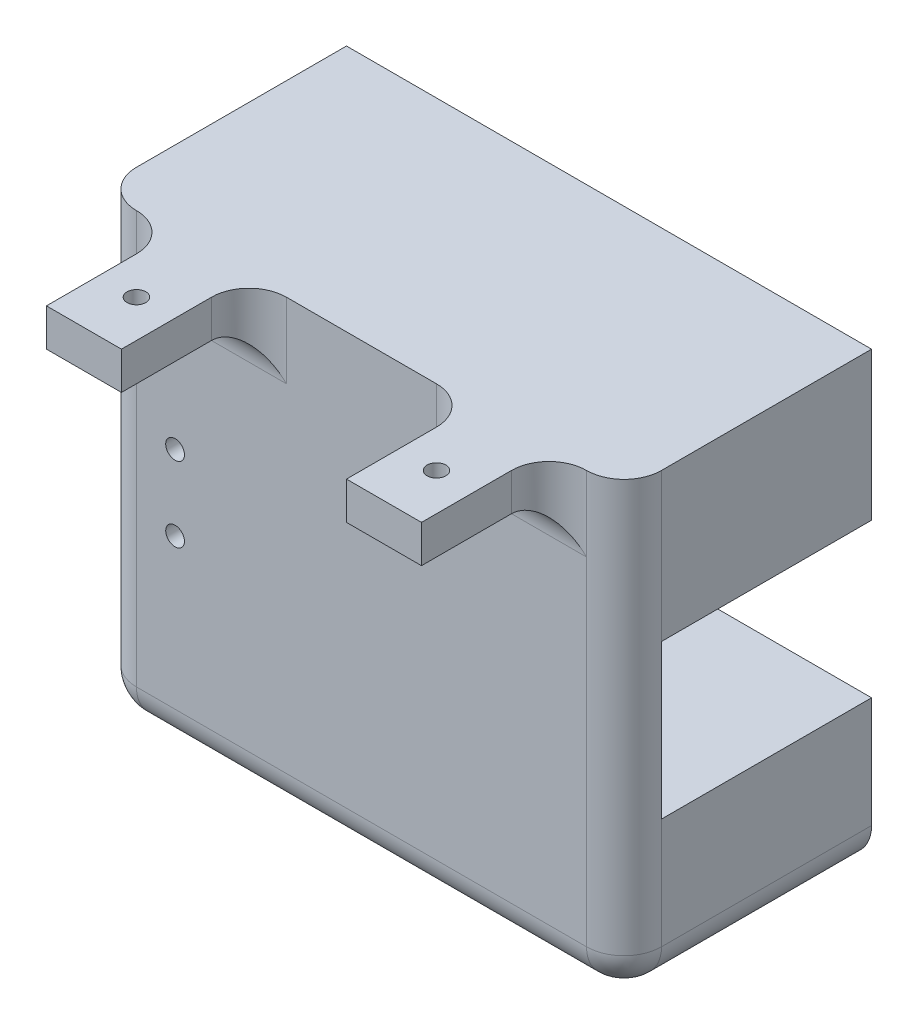
SolidWorks part; units mm, degrees
ref_plane "正面" through (0, 0, 0) normal (0, 0, 1) x (1, 0, 0)
ref_plane "平面" through (0, 0, 0) normal (0, 1, 0) x (1, 0, 0)
ref_plane "右側面" through (0, 0, 0) normal (1, 0, 0) x (0, 0, -1)
sketch "ｽｹｯﾁ2" plane through (0, 0, 0) normal (0, 0, 1) x (1, 0, 0)
  line L1 (-35, 30) -> (35, 30)
  line L2 (-35, 30) -> (-35, -30)
  line L3 (-35, -30) -> (35, -30)
  line L4 (35, 30) -> (35, -30)
  line L5 (-35, 30) -> (35, -30) construction
  line L6 (-35, -30) -> (35, 30) construction
  line L11 (-1.1602, 0.9945) -> (26.8884, -23.0472) construction
  line L12 (-15.8388, -9.5033) -> (15.8388, 9.5033) construction
  point P0 (0, 0)
  point P6 (0, 0)
  dimension "D1" = 70
  dimension "D2" = 60
extrude "ﾎﾞｽ - 押し出し2" add sketch "ｽｹｯﾁ2" along normal blind 33
sketch "ｽｹｯﾁ3" plane through (0, 0, 0) normal (0, 0, 1) x (1, 0, 0)
  line L1 (-20.35, 10.25) -> (20.35, 10.25)
  line L2 (-20.35, 10.25) -> (-20.35, -10.25)
  line L3 (-20.35, -10.25) -> (20.35, -10.25)
  line L4 (20.35, 10.25) -> (20.35, -10.25)
  line L5 (-20.35, 10.25) -> (20.35, -10.25) construction
  line L6 (-20.35, -10.25) -> (20.35, 10.25) construction
  point P0 (0, 0)
  dimension "D1" = 40.7
  dimension "D2" = 20.5
extrude "ｶｯﾄ - 押し出し1" cut sketch "ｽｹｯﾁ3" along normal blind 28 contours L2 L1 L4 L3
sketch "ｽｹｯﾁ4" plane through (0, 0, 0) normal (0, 0, 1) x (1, 0, 0)
  line L0 (20.35, 10.25) -> (35, 10.25)
  line L1 (35, -30) -> (35, 30) construction
  line L2 (35, 10.25) -> (35, -10.25)
  line L3 (35, -10.25) -> (20.35, -10.25)
  line L4 (20.35, -10.25) -> (20.35, 10.25)
extrude "ﾎﾞｽ - 押し出し3" add sketch "ｽｹｯﾁ4" along normal blind 28
sketch "ｽｹｯﾁ5" plane through (0, 0, 0) normal (0, 0, 1) x (1, 0, 0)
  line L0 (20.35, 10.25) -> (35, 10.25)
  line L1 (35, -30) -> (35, 30) construction
  line L2 (35, 10.25) -> (35, -10.25)
  line L3 (35, -10.25) -> (20.35, -10.25)
  line L4 (20.35, -10.25) -> (20.35, 10.25)
extrude "ｶｯﾄ - 押し出し4" cut sketch "ｽｹｯﾁ5" along normal blind 28
sketch "ｽｹｯﾁ6" plane through (0, 0, 0) normal (0, 0, 1) x (1, 0, 0)
  line L0 (-25, -30) -> (-25, -25)
  line L1 (-35, -30) -> (35, -30) construction
  line L2 (-25, -25) -> (-15, -25)
  line L3 (-15, -25) -> (-15, -30)
  line L4 (-15, -30) -> (-25, -30)
  line L5 (15, -25) -> (15, -30)
  line L6 (15, -30) -> (25, -30)
  line L7 (25, -30) -> (25, -25)
  line L8 (25, -25) -> (15, -25)
  dimension "D1" = 15
  dimension "D2" = 10
  dimension "D3" = 15
  dimension "D4" = 10
  dimension "D5" = 5
  dimension "D6" = 5
sketch "ｽｹｯﾁ8" plane through (0, 0, 0) normal (0, 0, 1) x (1, 0, 0)
  line L0 (-25, 30) -> (-25, 25)
  line L1 (35, 30) -> (-35, 30) construction
  line L2 (-25, 25) -> (-15, 25)
  line L3 (-15, 25) -> (-15, 30)
  line L4 (-15, 30) -> (-25, 30)
  line L5 (15, 30) -> (15, 25)
  line L6 (15, 25) -> (25, 25)
  line L7 (25, 25) -> (25, 30)
  line L8 (25, 30) -> (15, 30)
  dimension "D1" = 15
  dimension "D2" = 10
  dimension "D3" = 5
  dimension "D4" = 5
  dimension "D5" = 10
  dimension "D6" = 10
  dimension "D7" = 15
extrude "ﾎﾞｽ - 押し出し5" add sketch "ｽｹｯﾁ8" along normal blind 50
hole_wizard "M3x0.5 ねじ穴1" positions "ｽｹｯﾁ9" profile "ｽｹｯﾁ10" tap size "M3x0.5" standard "JIS" end condition through all
sketch "ｽｹｯﾁ9" plane through (0, 30, 0) normal (0, 1, 0) x (1, 0, 0)
  line L1 (15, -33) -> (-15, -33) construction
  line L2 (35, -33) -> (25, -33) construction
  point P0 (-20, -43)
  point P2 (20, -43)
  dimension "D1" = 10
  dimension "D2" = 10
  dimension "D3" = 20
  dimension "D4" = 20
sketch "ｽｹｯﾁ10" plane through (-20, 30, 43) normal (1, 0, 0) x (0, 0, 1)
  line L0 (0, 0) -> (0, 60)
  line L1 (0, 60) -> (1.25, 60)
  line L2 (1.25, 60) -> (1.25, 0)
  line L5 (1.25, 0) -> (0, 0)
  line L11 (0, -6.35) -> (0, 107.95) construction
  dimension "次ｻｰﾌｪｽまでのねじ下穴ﾄﾞﾘﾙ直径" = 2.5
  dimension "次ｻｰﾌｪｽまでのねじ下穴ﾄﾞﾘﾙの深さ" = 60
cosmetic thread "穴のねじ山1" parameters "D2"=3
cosmetic thread "穴のねじ山2" parameters "D2"=3
fillet "ﾌｨﾚｯﾄ1" radius 5 6 edges at (-25, 27.5, 33) (15, 27.5, 33) (-15, 27.5, 33) (25, 27.5, 33) (20, 25, 33) (-20, 25, 33)
fillet "ﾌｨﾚｯﾄ2" radius 5 4 edges at (35, 0, 33) (35, -30, 16.5) (0, -30, 33) (-35, 0, 33)
fillet "ﾌｨﾚｯﾄ3" radius 5 2 edges at (-33.5355, -28.5355, 31.5355) (-35, -30, 14)
hole_wizard "M3x0.5 ねじ穴2" positions "ｽｹｯﾁ12" profile "ｽｹｯﾁ13" tap size "M3x0.5" standard "JIS" end condition through all
sketch "ｽｹｯﾁ12" plane through (0, 0, 0) normal (0, 0, -1) x (-1, 0, 0)
  line L0 (20.35, 10.25) -> (20.35, -10.25) construction
  point P0 (24.85, 5)
  point P2 (24.85, -5)
  dimension "D1" = 10
  dimension "D2" = 5
  dimension "D3" = 24.85
  dimension "D4" = 4.5
sketch "ｽｹｯﾁ13" plane through (-24.85, 5, 0) normal (1, 0, 0) x (0, 1, 0)
  line L0 (0, 0) -> (0, 50)
  line L1 (0, 50) -> (1.25, 50)
  line L2 (1.25, 50) -> (1.25, 0)
  line L5 (1.25, 0) -> (0, 0)
  line L11 (0, -6.35) -> (0, 107.95) construction
  dimension "次ｻｰﾌｪｽまでのねじ下穴ﾄﾞﾘﾙ直径" = 2.5
  dimension "次ｻｰﾌｪｽまでのねじ下穴ﾄﾞﾘﾙの深さ" = 50
cosmetic thread "穴のねじ山3" parameters "D2"=3
cosmetic thread "穴のねじ山4" parameters "D2"=3
